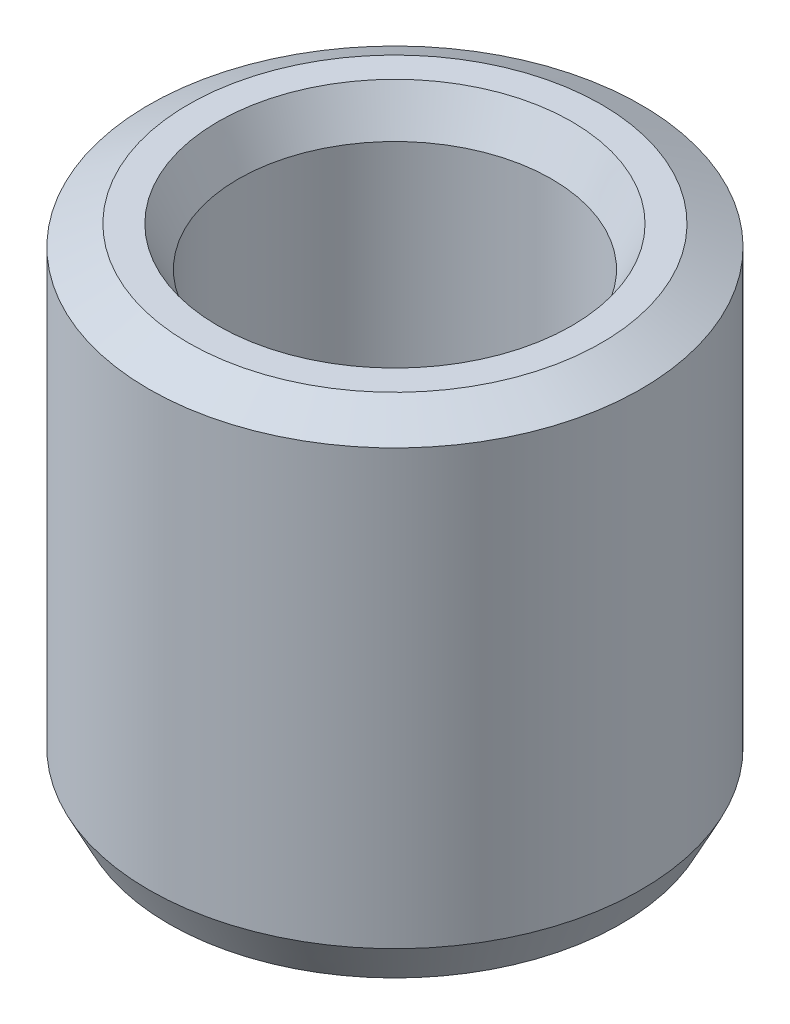
SolidWorks part; units mm, degrees
ref_plane "Front Plane" through (0, 0, 0) normal (0, 0, 1) x (1, 0, 0)
ref_plane "Top Plane" through (0, 0, 0) normal (0, 1, 0) x (1, 0, 0)
ref_plane "Right Plane" through (0, 0, 0) normal (1, 0, 0) x (0, 0, -1)
sketch "Sketch1" plane through (0, 0, 0) normal (0, 1, 0) x (1, 0, 0)
  circle A0 centre (0, 0) radius 37.5
  dimension "SLEEVE_OD" = 75
extrude "Boss-Extrude1" add sketch "Sketch1" along normal blind 75.1759
sketch "Sketch2" plane through (0, 0, 0) normal (0, 1, 0) x (1, 0, 0)
  circle A0 centre (0, 0) radius 23.8707
  dimension "BORE_D" = 47.7414
extrude "Cut-Extrude1" cut sketch "Sketch2" along normal through all
chamfer "Chamfer1" distance 3.0735 angle 63.013 4 edges at (0, 75.1759, 23.8707) (0, 0, 23.8707) (0, 0, 37.5) (0, 75.1759, 37.5) first distance on face at (0, 75.1759, 23.8707) first distance on face at (0, 0, 23.8707) first distance on face at (0, 75.1759, 37.5)
